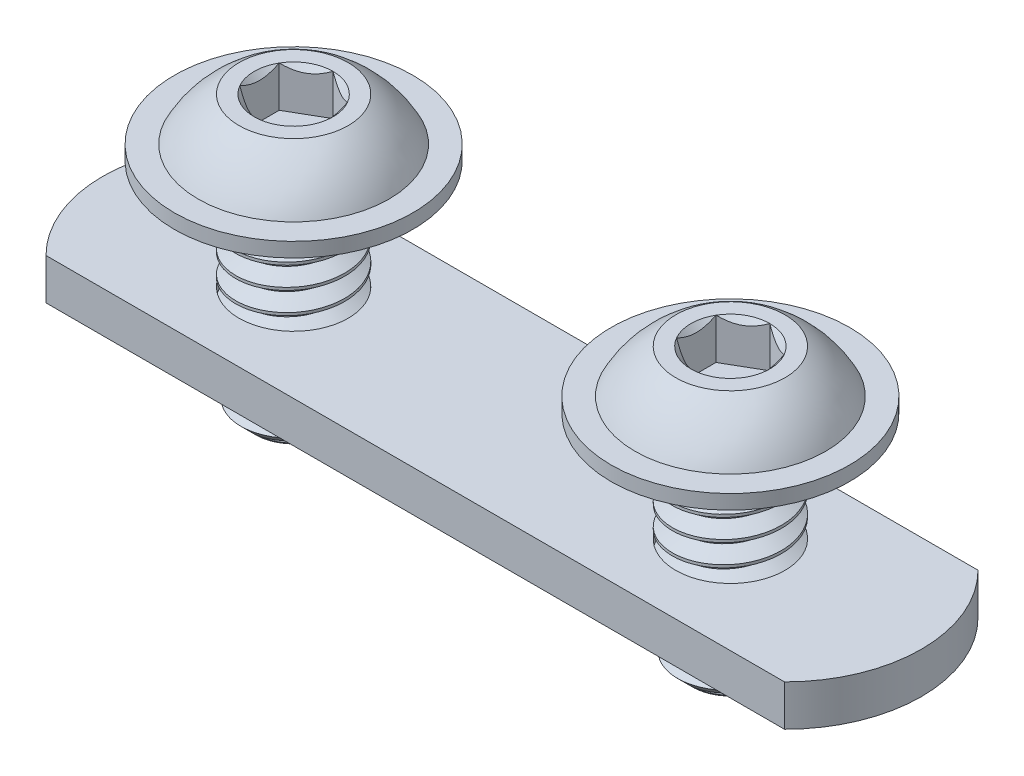
SolidWorks part; units mm, degrees
ref_plane "Front Plane" through (0, 0, 0) normal (0, 0, 1) x (1, 0, 0)
ref_plane "Top Plane" through (0, 0, 0) normal (0, 1, 0) x (1, 0, 0)
ref_plane "Right Plane" through (0, 0, 0) normal (1, 0, 0) x (0, 0, -1)
sketch "Sketch1" plane through (0, 0, 0) normal (0, 1, 0) x (1, 0, 0)
  line L0 (-12.7, 0) -> (12.7, 0) construction
  circle A0 centre (-12.7, 0) radius 3.175
  point P3 (-15.875, 0)
  point P4 (-9.525, 0)
  dimension "D1" = 6.35
  dimension "D2" = 25.4
extrude "Boss-Extrude1" add sketch "Sketch1" against normal blind 12.7
sketch "Sketch2" plane through (0, -12.7, 0) normal (0, -1, 0) x (1, 0, 0)
  circle A1 centre (-12.7, 0) radius 3.175
  circle A2 centre (-12.7, 0) radius 3.175
  point P0 (-12.7, -3.175)
  dimension "D1" = 0
curve "Helix/Spiral1" pitch 1.27 height 13.97 turns 11
ref_plane "Plane1" through (-12.7, 0, 0) normal (1, 0, 0) x (0, 0, -1)
sketch "Sketch3" plane through (-12.7, 0, 0) normal (1, 0, 0) x (0, 0, -1)
  line L0 (3.3125, -12.6206) -> (2.2126, -13.2556) construction
  line L1 (2.2126, -13.2556) -> (3.3125, -13.8906) construction
  line L2 (3.3125, -13.8906) -> (3.3125, -12.6206) construction
  line L3 (2.3501, -13.1762) -> (2.3501, -13.335) construction
  line L4 (3.175, -12.7) -> (3.175, -13.8112) construction
  line L5 (2.2126, -13.2556) -> (2.3501, -13.2556) construction
  line L6 (3.175, -13.2556) -> (3.3125, -13.2556) construction
  line L8 (2.2126, -13.2556) -> (-3.175, -13.2556) construction
  line L9 (2.3501, -13.1762) -> (3.2437, -12.6603)
  line L10 (2.3501, -13.1762) -> (2.3501, -13.335)
  line L11 (2.3501, -13.335) -> (3.2437, -13.8509)
  line L12 (3.2437, -13.8509) -> (3.2437, -12.6603)
  line L14 (-3.175, -13.2556) -> (-3.175, -11.9856) construction
  line L15 (-3.175, -11.9856) -> (-3.175, -10.7156) construction
  line L16 (-3.175, -10.7156) -> (-3.175, -9.4456) construction
  line L17 (-3.175, -9.4456) -> (-3.175, -8.1756) construction
  line L18 (-3.175, 0) -> (-3.175, -12.7) construction
  point P15 (3.2437, -13.2556)
  dimension "D1" = 1.27
  dimension "D2" = 0.1588
sweep "Cut-Sweep1" cut profiles "Sketch3" path "Helix/Spiral1"
sketch "Sketch4" plane through (0, -12.7, 0) normal (0, -1, 0) x (1, 0, 0)
  circle A0 centre (-12.7, 0) radius 2.2126
extrude "Cut-Extrude1" cut sketch "Sketch4" against normal blind 1.27 draft 45 flip side to cut
sketch "Sketch5" plane through (0, 0, 0) normal (0, 0, 1) x (1, 0, 0)
  line L0 (-12.7, 0) -> (-12.7, 3.3528)
  line L1 (-19.6342, 0) -> (-12.7, 0)
  line L2 (-12.7, 3.3528) -> (-15.875, 3.3528)
  line L3 (-18.2499, 0.8382) -> (-19.6342, 0.8382)
  line L4 (-19.6342, 0.8382) -> (-19.6342, 0)
  line L5 (-12.7, 0) -> (-12.7, -12.7) construction
  arc A0 (-15.875, 3.3528) -> (-18.2499, 0.8382) centre (-12.7, -2.0246) ccw
  dimension "D1" = 3.3528
  dimension "D2" = 0.8382
  dimension "D3" = 13.8684
  dimension "D4" = 11.0998
revolve "Revolve1" add sketch "Sketch5" angle 360 mid plane about L0
sketch "Sketch6" plane through (0, 3.3528, 0) normal (0, 1, 0) x (1, 0, 0)
  line L1 (-12.7, 2.2914) -> (-14.6844, 1.1457)
  line L2 (-14.6844, 1.1457) -> (-14.6844, -1.1457)
  line L3 (-14.6844, -1.1457) -> (-12.7, -2.2914)
  line L4 (-12.7, -2.2914) -> (-10.7156, -1.1457)
  line L5 (-10.7156, -1.1457) -> (-10.7156, 1.1457)
  line L6 (-10.7156, 1.1457) -> (-12.7, 2.2914)
  circle A0 centre (-12.7, 0) radius 1.9844 construction
  dimension "D1" = 3.9688
extrude "Cut-Extrude2" cut sketch "Sketch6" against normal blind 2.3813
sketch "Sketch7" plane through (0, 3.3528, 0) normal (0, 1, 0) x (1, 0, 0)
  circle A0 centre (-12.7, 0) radius 2.2914
extrude "Cut-Extrude3" cut sketch "Sketch7" against normal blind 2.3813 draft 45
move or copy body "Body-Move/Copy1" bodies to move or copy 110 copy yes number of copies 1 translate (25.4, 0, 0)
sketch "Sketch8" plane through (0, 0, 0) normal (0, 1, 0) x (1, 0, 0)
  line L0 (-23.8125, 0) -> (23.8125, 0) construction
  line L1 (-21.4742, 5.6261) -> (21.4742, 5.6261)
  line L2 (-21.4742, -5.6261) -> (21.4742, -5.6261)
  line L4 (-23.8125, 5.6261) -> (23.8125, 5.6261) construction
  line L5 (-23.8125, 5.6261) -> (-23.8125, -5.6261) construction
  line L6 (-23.8125, -5.6261) -> (23.8125, -5.6261) construction
  line L7 (23.8125, 5.6261) -> (23.8125, -5.6261) construction
  arc A0 (-21.4742, 5.6261) -> (-21.4742, -5.6261) centre (-15.875, 0) ccw
  arc A1 (21.4742, 5.6261) -> (21.4742, -5.6261) centre (15.875, 0) cw
  circle A3 centre (-12.7, 0) radius 3.175
  circle A4 centre (-12.7, 0) radius 3.175
  circle A5 centre (12.7, 0) radius 3.175
  dimension "D2" = 47.625
  dimension "D4" = 7.9375
  dimension "D3" = 11.2522
  dimension "D1" = 0
extrude "Boss-Extrude2" add sketch "Sketch8" against normal blind 2.3876 from offset 6.35 separate body offset against normal yes
sketch "Sketch9" plane through (0, -8.7376, 0) normal (0, -1, 0) x (1, 0, 0)
  circle A0 centre (12.7, 0) radius 3.175
  circle A1 centre (-12.7, 0) radius 3.175 construction
  circle A2 centre (-12.7, 0) radius 3.175
  circle A3 centre (-12.7, 0) radius 3.5687
  circle A4 centre (12.7, 0) radius 3.5687
  dimension "D1" = 7.1374
extrude "Boss-Extrude3" add sketch "Sketch9" along normal blind 0.762
sketch "SketchZ" plane through (0, 0, 0) normal (0, 0, 1) x (1, 0, 0)
  line L0 (-9.525, -12.9381) -> (-9.525, -11.6681) construction
  line L2 (-12.7, -13.2556) -> (-12.7, -11.9856) construction
  line L4 (-9.525, -12.9381) -> (-12.7, -12.9381) construction
  line L5 (-12.7, -9.4456) -> (-12.7, -8.1756) construction
  line L6 (-12.7, -12.6206) -> (-12.7, -13.2556) construction
equation "\"D3@Helix/Spiral1\" = \"D4@Helix/Spiral1\" + \"D1@Boss-Extrude1\""
equation "\"D1@Sketch3\" = \"D4@Helix/Spiral1\""
equation "\"D2@Sketch3\" = \"D1@Sketch3\" / 8"
equation "\"D1@Cut-Extrude1\" = \"D4@Helix/Spiral1\""
equation "\"D1@Cut-Extrude2\" = \"D1@Sketch6\" * 3/5"
equation "\"D1@Cut-Extrude3\" = \"D1@Cut-Extrude2\""
equation "\"D2@Sketch5\" = \"D1@Sketch5\" * 1/4"
